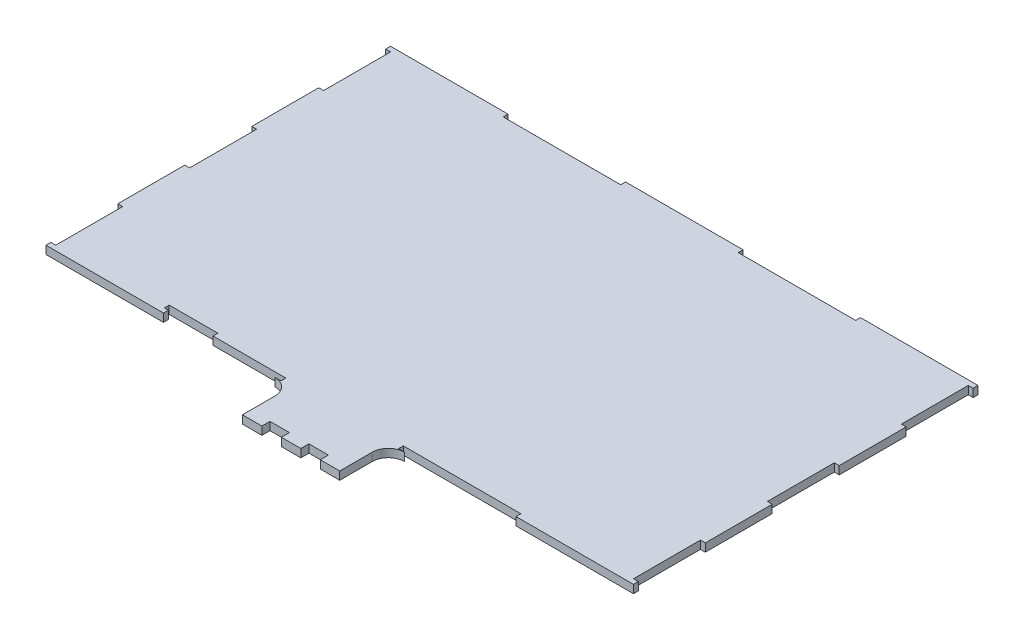
SolidWorks part; units mm, degrees
ref_plane "Front Plane" through (0, 0, 0) normal (0, 0, 1) x (1, 0, 0)
ref_plane "Top Plane" through (0, 0, 0) normal (0, 1, 0) x (1, 0, 0)
ref_plane "Right Plane" through (0, 0, 0) normal (1, 0, 0) x (0, 0, -1)
sketch "Sketch1" plane through (0, 0, 0) normal (0, 1, 0) x (1, 0, 0)
  line L0 (-30, -136.2503) -> (-18, -136.2503)
  line L5 (-181.15, 106.25) -> (181.15, -106.25) construction
  line L6 (-181.15, -106.25) -> (181.15, 106.25) construction
  line L13 (-30, -116.25) -> (-30, -136.2503)
  line L17 (30, -136.2503) -> (30, -116.25)
  line L18 (-18, -131.2503) -> (-6, -131.2503)
  line L20 (18, -136.2503) -> (30, -136.2503)
  line L21 (-6, -136.2503) -> (6, -136.2503)
  line L23 (-18, -136.2503) -> (-18, -131.2503)
  line L24 (-6, -136.2503) -> (-6, -131.2503)
  line L25 (6, -136.2503) -> (6, -131.2503)
  line L26 (18, -136.2503) -> (18, -131.2503)
  line L28 (6, -131.2503) -> (18, -131.2503)
  line L54 (-181.15, 106.25) -> (-181.15, 103.25) construction
  line L55 (181.15, 106.25) -> (108.69, 106.25)
  line L60 (-181.15, -106.25) -> (-181.15, -103.25)
  line L62 (-181.15, 103.25) -> (181.15, 103.25) construction
  line L63 (-108.69, 103.2497) -> (-36.23, 103.2497)
  line L64 (36.23, 106.25) -> (-36.23, 106.25)
  line L65 (36.23, 103.2497) -> (108.69, 103.2497)
  line L66 (-108.69, 103.2497) -> (-108.69, 106.25)
  line L67 (-36.23, 103.2497) -> (-36.23, 106.25)
  line L68 (36.23, 103.2497) -> (36.23, 106.25)
  line L69 (108.69, 103.2497) -> (108.69, 106.25)
  line L70 (-108.69, 106.25) -> (-181.15, 106.25)
  line L71 (-181.15, -103.25) -> (-178.15, -103.25)
  line L72 (-108.69, -106.25) -> (-108.69, -103.25)
  line L73 (-178.15, -103.25) -> (-178.15, -61.95)
  line L74 (-181.15, -61.95) -> (-181.15, -20.65)
  line L75 (-178.15, -20.65) -> (-178.15, 20.65)
  line L76 (-181.15, 20.65) -> (-181.15, 61.95)
  line L77 (-178.15, 61.95) -> (-178.15, 103.25)
  line L78 (-178.15, 61.95) -> (-181.15, 61.95)
  line L79 (-178.15, 20.65) -> (-181.15, 20.65)
  line L80 (-178.15, -20.65) -> (-181.15, -20.65)
  line L81 (-178.15, -61.95) -> (-181.15, -61.95)
  line L82 (-181.15, 103.25) -> (-181.15, 106.25)
  line L83 (-181.15, 103.25) -> (-178.15, 103.25)
  line L84 (-36.23, -106.25) -> (-40, -106.25)
  line L85 (181.15, -103.25) -> (178.15, -103.25)
  line L86 (178.15, -103.25) -> (178.15, -61.95)
  line L87 (178.15, -61.95) -> (181.15, -61.95)
  line L88 (181.15, -61.95) -> (181.15, -20.65)
  line L89 (178.15, -20.65) -> (181.15, -20.65)
  line L90 (178.15, -20.65) -> (178.15, 20.65)
  line L91 (178.15, 20.65) -> (181.15, 20.65)
  line L92 (181.15, 20.65) -> (181.15, 61.95)
  line L93 (178.15, 61.95) -> (181.15, 61.95)
  line L94 (178.15, 61.95) -> (178.15, 103.25)
  line L95 (181.15, 103.25) -> (178.15, 103.25)
  line L96 (181.15, -106.25) -> (181.15, -103.25)
  line L97 (181.15, 103.25) -> (181.15, 106.25)
  line L98 (-181.15, -106.25) -> (-108.69, -106.25)
  line L99 (108.69, -103.2497) -> (108.69, -106.25)
  line L100 (36.23, -103.2497) -> (108.69, -103.2497)
  line L101 (36.23, -103.2497) -> (36.23, -106.25)
  line L102 (40, -106.25) -> (36.23, -106.25)
  line L103 (-36.23, -103.2497) -> (-36.23, -106.25)
  line L106 (108.69, -106.25) -> (181.15, -106.25)
  line L107 (-81.15, -100.25) -> (-111.15, -100.25)
  line L108 (-81.15, -103.2497) -> (-36.23, -103.2497)
  line L109 (-108.69, -103.25) -> (-111.15, -103.25)
  line L111 (-81.15, -100.25) -> (-81.15, -103.2497)
  line L112 (-111.15, -100.25) -> (-111.15, -103.25)
  arc A0 (-40, -106.25) -> (-30, -116.25) centre (-40, -116.25) cw
  arc A1 (40, -106.25) -> (30, -116.25) centre (40, -116.25) ccw
  point P0 (0, 0)
  dimension "D3" = 10
  dimension "D4" = 10
  dimension "D1" = 212.5
extrude "Boss-Extrude1" add sketch "Sketch1" along normal blind 5
